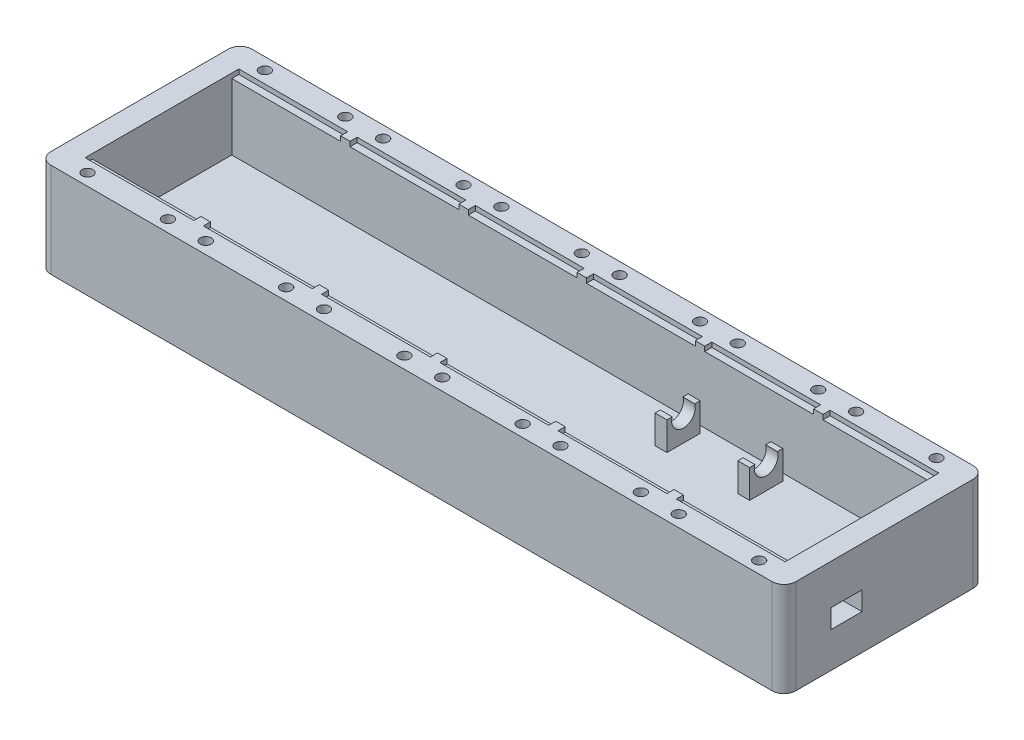
SolidWorks part; units mm, degrees
material "Starkstromplatine"
ref_plane "Ebene vorne" through (0, 0, 0) normal (0, 0, 1) x (1, 0, 0)
ref_plane "Ebene oben" through (0, 0, 0) normal (0, 1, 0) x (1, 0, 0)
ref_plane "Ebene rechts" through (0, 0, 0) normal (1, 0, 0) x (0, 0, -1)
sketch "Skizze2" plane through (0, 0, 0) normal (0, 0, 1) x (1, 0, 0)
  line L1 (0, 0) -> (315, 0)
  line L2 (0, 0) -> (0, 40)
  line L3 (0, 40) -> (315, 40)
  line L4 (315, 0) -> (315, 40)
  dimension "D1" = 315
  dimension "D2" = 40
extrude "Aufsatz-Linear austragen1" add sketch "Skizze2" along normal blind 85
sketch "Skizze4" plane through (0, 40, 0) normal (0, 1, 0) x (1, 0, 0)
  line L1 (9.5, -13) -> (305.5, -13)
  line L2 (9.5, -13) -> (9.5, -72)
  line L3 (9.5, -72) -> (305.5, -72)
  line L4 (305.5, -13) -> (305.5, -72)
  line L6 (0, -85) -> (0, 0) construction
  line L7 (315, -85) -> (315, 0) construction
  line L8 (315, -85) -> (0, -85) construction
  dimension "D1" = 59
  dimension "D2" = 13
  dimension "D3" = 9.5
  dimension "D4" = 9.5
extrude "Schnitt-Linear austragen1" cut sketch "Skizze4" against normal blind 30
sketch "Skizze11" plane through (0, 40, 0) normal (0, 1, 0) x (1, 0, 0)
  line L0 (9.5, -72) -> (305.5, -72) construction
  line L1 (9.5, -13) -> (55.5, -13)
  line L2 (9.5, -13) -> (9.5, -10)
  line L3 (9.5, -10) -> (55.5, -10)
  line L4 (55.5, -13) -> (55.5, -10)
  line L5 (55.5, -72) -> (9.5, -72)
  line L6 (55.5, -72) -> (55.5, -75)
  line L7 (55.5, -75) -> (9.5, -75)
  line L8 (9.5, -72) -> (9.5, -75)
  line L9 (305.5, -13) -> (9.5, -13) construction
  line L10 (59.5, -75) -> (105.5, -75)
  line L11 (59.5, -75) -> (59.5, -72)
  line L12 (59.5, -72) -> (105.5, -72)
  line L13 (105.5, -75) -> (105.5, -72)
  line L14 (109.5, -75.0087) -> (155.5, -75.0087)
  line L15 (109.5, -75.0087) -> (109.5, -72)
  line L16 (109.5, -72) -> (155.5, -72)
  line L17 (155.5, -75.0087) -> (155.5, -72)
  line L18 (159.5, -75.0087) -> (205.5, -75.0087)
  line L19 (159.5, -75.0087) -> (159.5, -72)
  line L20 (159.5, -72) -> (205.5, -72)
  line L21 (205.5, -75.0087) -> (205.5, -72)
  line L22 (209.5, -75) -> (255.5, -75)
  line L23 (209.5, -75) -> (209.5, -72)
  line L24 (209.5, -72) -> (255.5, -72)
  line L25 (255.5, -75) -> (255.5, -72)
  line L26 (259.5, -75) -> (305.5, -75)
  line L27 (259.5, -75) -> (259.5, -72)
  line L28 (259.5, -72) -> (305.5, -72)
  line L29 (305.5, -75) -> (305.5, -72)
  line L30 (305.5, -13) -> (259.5, -13)
  line L31 (305.5, -13) -> (305.5, -10)
  line L32 (305.5, -10) -> (259.5, -10)
  line L33 (259.5, -13) -> (259.5, -10)
  line L35 (255.5, -13) -> (209.5, -13)
  line L36 (255.5, -13) -> (255.5, -10)
  line L37 (255.5, -10) -> (209.5, -10)
  line L38 (209.5, -13) -> (209.5, -10)
  line L39 (205.5, -13) -> (159.5, -13)
  line L40 (205.5, -13) -> (205.5, -10)
  line L41 (205.5, -10) -> (159.5, -10)
  line L42 (159.5, -13) -> (159.5, -10)
  line L43 (155.5, -13) -> (109.5, -13)
  line L44 (155.5, -13) -> (155.5, -10)
  line L45 (155.5, -10) -> (109.5, -10)
  line L46 (109.5, -13) -> (109.5, -10)
  line L47 (105.5, -13) -> (59.5, -13)
  line L48 (105.5, -13) -> (105.5, -10)
  line L49 (105.5, -10) -> (59.5, -10)
  line L50 (59.5, -13) -> (59.5, -10)
  line L56 (315, -85) -> (315, 0) construction
  dimension "D1" = 46
  dimension "D2" = 3
  dimension "D3" = 46
  dimension "D4" = 4
  dimension "D5" = 4
  dimension "D6" = 4
  dimension "D7" = 4
  dimension "D8" = 4
  dimension "D9" = 4
  dimension "D10" = 46
  dimension "D11" = 46
  dimension "D12" = 46
  dimension "D13" = 46
  dimension "D14" = 46
  dimension "D15" = 4
  dimension "D16" = 4
  dimension "D17" = 4
  dimension "D18" = 4
  dimension "D19" = 46
  dimension "D20" = 46
  dimension "D21" = 46
  dimension "D22" = 46
  dimension "D23" = 3
  dimension "D24" = 3
  dimension "D25" = 3
  dimension "D26" = 3
  dimension "D27" = 3
  dimension "D28" = 3
  dimension "D29" = 3
  dimension "D30" = 3
  dimension "D31" = 46
  dimension "D32" = 9.5
extrude "Schnitt-Linear austragen4" cut sketch "Skizze11" against normal blind 2
sketch "Skizze17" plane through (0, 40, 0) normal (0, 1, 0) x (1, 0, 0)
  line L0 (55.5, -75) -> (55.5, -72) construction
  line L1 (315, 0) -> (0, 0) construction
  line L2 (315, -85) -> (0, -85) construction
  line L3 (9.5, -72) -> (9.5, -75) construction
  line L4 (9.5, -10) -> (9.5, -75) construction
  line L5 (55.5, -13) -> (55.5, -10) construction
  line L6 (59.5, -72) -> (59.5, -75) construction
  line L7 (105.5, -75) -> (105.5, -72) construction
  line L8 (155.5, -75.0087) -> (155.5, -72) construction
  line L9 (105.5, -13) -> (105.5, -10) construction
  line L10 (159.5, -72) -> (159.5, -75.0087) construction
  line L11 (205.5, -75.0087) -> (205.5, -72) construction
  line L12 (305.5, -75) -> (305.5, -10) construction
  line L13 (259.5, -72) -> (259.5, -75) construction
  line L14 (255.5, -75) -> (255.5, -72) construction
  line L15 (209.5, -72) -> (209.5, -75) construction
  line L16 (59.5, -10) -> (59.5, -13) construction
  line L17 (155.5, -13) -> (155.5, -10) construction
  line L18 (109.5, -10) -> (109.5, -13) construction
  line L19 (159.5, -10) -> (159.5, -13) construction
  line L20 (209.5, -10) -> (209.5, -13) construction
  line L21 (255.5, -13) -> (255.5, -10) construction
  line L22 (259.5, -10) -> (259.5, -13) construction
  line L23 (305.5, -13) -> (305.5, -10) construction
  line L24 (109.5, -72) -> (109.5, -75.0087) construction
  circle A0 centre (49.5, -80) radius 2.3
  circle A1 centre (15.5, -80) radius 2.3
  circle A2 centre (15.5, -5) radius 2.3
  circle A3 centre (49.5, -5) radius 2.3
  circle A4 centre (65.5, -5) radius 2.3
  circle A5 centre (99.5, -5) radius 2.3
  circle A6 centre (65.5, -80) radius 2.3
  circle A7 centre (99.5, -80) radius 2.3
  circle A8 centre (115.5, -80) radius 2.3
  circle A9 centre (149.5, -80) radius 2.3
  circle A10 centre (165.5, -80) radius 2.3
  circle A11 centre (199.5, -80) radius 2.3
  circle A12 centre (215.5, -80) radius 2.3
  circle A13 centre (249.5, -80) radius 2.3
  circle A14 centre (265.5, -80) radius 2.3
  circle A15 centre (299.5, -80) radius 2.3
  circle A16 centre (299.5, -5) radius 2.3
  circle A17 centre (265.5, -5) radius 2.3
  circle A18 centre (249.5, -5) radius 2.3
  circle A19 centre (215.5, -5) radius 2.3
  circle A20 centre (199.5, -5) radius 2.3
  circle A21 centre (165.5, -5) radius 2.3
  circle A22 centre (149.5, -5) radius 2.3
  circle A23 centre (115.5, -5) radius 2.3
  dimension "D1" = 4.6
  dimension "D2" = 4.6
  dimension "D3" = 4.6
  dimension "D4" = 4.6
  dimension "D5" = 5
  dimension "D6" = 5
  dimension "D7" = 5
  dimension "D8" = 5
  dimension "D10" = 6
  dimension "D11" = 6
  dimension "D12" = 6
  dimension "D13" = 4.6
  dimension "D14" = 4.6
  dimension "D15" = 4.6
  dimension "D16" = 4.6
  dimension "D17" = 4.6
  dimension "D18" = 4.6
  dimension "D19" = 4.6
  dimension "D20" = 4.6
  dimension "D21" = 4.6
  dimension "D22" = 4.6
  dimension "D23" = 6
  dimension "D25" = 5
  dimension "D26" = 5
  dimension "D27" = 6
  dimension "D28" = 5
  dimension "D29" = 6
  dimension "D30" = 5
  dimension "D31" = 6
  dimension "D32" = 5
  dimension "D33" = 5
  dimension "D34" = 5
  dimension "D35" = 5
  dimension "D36" = 5
  dimension "D37" = 6
  dimension "D38" = 6
  dimension "D39" = 6
  dimension "D40" = 6
  dimension "D41" = 5
  dimension "D42" = 6
  dimension "D43" = 4.6
  dimension "D44" = 4.6
  dimension "D45" = 4.6
  dimension "D46" = 4.6
  dimension "D47" = 4.6
  dimension "D48" = 4.6
  dimension "D49" = 4.6
  dimension "D50" = 4.6
  dimension "D51" = 4.6
  dimension "D52" = 4.6
  dimension "D53" = 5
  dimension "D54" = 6
  dimension "D55" = 5
  dimension "D56" = 6
  dimension "D58" = 6
  dimension "D62" = 6
  dimension "D63" = 6
  dimension "D64" = 6
  dimension "D9" = 6
  dimension "D24" = 6
  dimension "D57" = 6
  dimension "D59" = 6
  dimension "D60" = 6
  dimension "D61" = 6
extrude "Schnitt-Linear austragen6" cut sketch "Skizze17" against normal blind 4
fillet "Verrundung2" radius 5 1 edges at (0, 20, 85)
fillet "Verrundung3" radius 5 1 edges at (0, 20, 0)
fillet "Verrundung4" radius 5 1 edges at (315, 20, 0)
fillet "Verrundung6" radius 5 1 edges at (315, 20, 85)
sketch "Skizze18" plane through (305.5, 0, 0) normal (-1, 0, 0) x (0, 0, 1)
  line L0 (72, 10) -> (72, 38) construction
  line L1 (52, 23) -> (65, 23)
  line L2 (52, 23) -> (52, 15)
  line L3 (52, 15) -> (65, 15)
  line L4 (65, 23) -> (65, 15)
  line L5 (72, 10) -> (13, 10) construction
  dimension "D1" = 7
  dimension "D2" = 13
  dimension "D3" = 8
  dimension "D4" = 5
  dimension "D5" = 5
extrude "Schnitt-Linear austragen7" cut sketch "Skizze18" against normal blind 10
sketch "Skizze20" plane through (0, 10, 0) normal (0, 1, 0) x (1, 0, 0)
  line L0 (305.5, -13) -> (9.5, -13) construction
  line L1 (240.5, -16) -> (245.5, -16)
  line L2 (240.5, -16) -> (240.5, -30)
  line L3 (240.5, -30) -> (245.5, -30)
  line L4 (245.5, -16) -> (245.5, -30)
  line L5 (205.5, -16) -> (210.5, -16)
  line L6 (205.5, -16) -> (205.5, -30)
  line L7 (205.5, -30) -> (210.5, -30)
  line L8 (210.5, -16) -> (210.5, -30)
  line L9 (305.5, -72) -> (305.5, -13) construction
  dimension "D1" = 14
  dimension "D2" = 14
  dimension "D3" = 5
  dimension "D4" = 5
  dimension "D5" = 3
  dimension "D6" = 3
  dimension "D7" = 30
  dimension "D8" = 60
extrude "Aufsatz-Linear austragen2" add sketch "Skizze20" along normal blind 12
sketch "Skizze21" plane through (205.5, 0, 0) normal (-1, 0, 0) x (0, 0, 1)
  line L0 (16, 22) -> (16, 10) construction
  line L1 (16, 22) -> (30, 22) construction
  circle A0 centre (23, 20.5) radius 5
  dimension "D1" = 7
  dimension "D2" = 1.5
extrude "Schnitt-Linear austragen8" cut sketch "Skizze21" against normal blind 71
